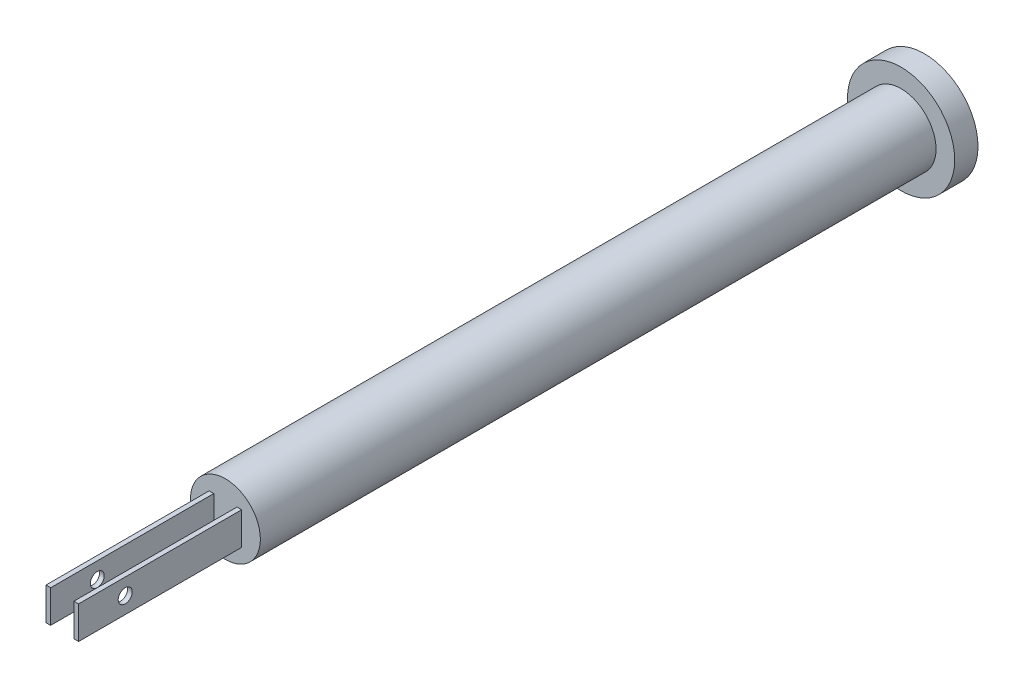
SolidWorks part; units mm, degrees
ref_plane "Front Plane" through (0, 0, 0) normal (0, 0, 1) x (1, 0, 0)
ref_plane "Top Plane" through (0, 0, 0) normal (0, 1, 0) x (1, 0, 0)
ref_plane "Right Plane" through (0, 0, 0) normal (1, 0, 0) x (0, 0, -1)
sketch "Sketch1" plane through (0, 0, 0) normal (0, 0, 1) x (1, 0, 0)
  circle A0 centre (0, 0) radius 11.5
  circle A1 centre (0, 0) radius 7.5
  dimension "D1" = 23
  dimension "D2" = 15
extrude "Boss-Extrude2" add sketch "Sketch1" along normal blind 150 contours A1
extrude "Boss-Extrude3" add sketch "Sketch1<4>" along normal blind 5
sketch "Sketch1<4>" plane through (0, 0, 0) normal (0, 0, 1) x (1, 0, 0) same geometry as "Sketch1"
sketch "Sketch3" plane through (0, 0, 150) normal (0, 0, 1) x (1, 0, 0)
  line L1 (-3.5, -3.5) -> (3.5, -3.5)
  line L2 (-3.5, -3.5) -> (-3.5, 3.5)
  line L3 (-3.5, 3.5) -> (3.5, 3.5)
  line L4 (3.5, -3.5) -> (3.5, 3.5)
  line L5 (-3.5, -3.5) -> (3.5, 3.5) construction
  line L6 (-3.5, 3.5) -> (3.5, -3.5) construction
  point P0 (0, 0)
  dimension "D1" = 7
extrude "Boss-Extrude4" add sketch "Sketch3" along normal blind 35
sketch "Sketch7" plane through (0, 3.5, 0) normal (0, 1, 0) x (1, 0, 0)
  line L0 (3.5, -150) -> (-3.5, -150) construction
  line L1 (-2.5, -150) -> (2.5, -150)
  line L2 (-2.5, -150) -> (-2.5, -185)
  line L3 (-2.5, -185) -> (2.5, -185)
  line L4 (2.5, -150) -> (2.5, -185)
  line L5 (3.5, -185) -> (-3.5, -185) construction
  point P8 (0, -150)
  point P9 (0, -150)
  dimension "D1" = 5
extrude "Cut-Extrude2" cut sketch "Sketch7" against normal blind 10
sketch "Sketch8" plane through (3.5, 0, 0) normal (1, 0, 0) x (0, 0, -1)
  line L0 (-185, -3.5) -> (-185, 3.5) construction
  circle A0 centre (-175, 0) radius 1.5
  point P2 (0, 0)
  point P5 (-185, 0)
  dimension "D1" = 3
  dimension "D2" = 10
extrude "Cut-Extrude3" cut sketch "Sketch8" against normal blind 10
